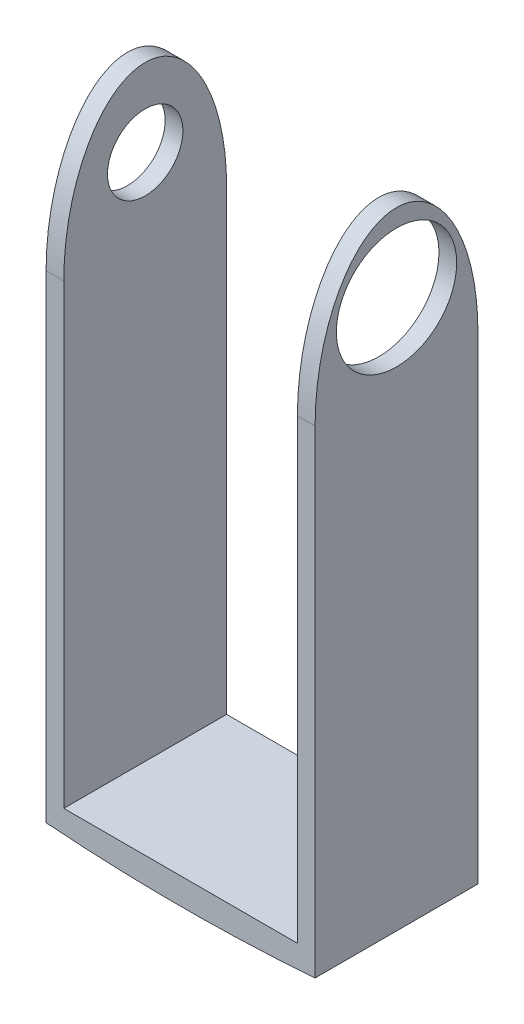
SolidWorks part; units mm, degrees
ref_plane "Front Plane" through (0, 0, 0) normal (0, 0, 1) x (1, 0, 0)
ref_plane "Top Plane" through (0, 0, 0) normal (0, 1, 0) x (1, 0, 0)
ref_plane "Right Plane" through (0, 0, 0) normal (1, 0, 0) x (0, 0, -1)
sketch "Sketch1" plane through (0, 0, 0) normal (0, 0, 1) x (1, 0, 0)
  line L0 (-3.3539, 20.1872) -> (-3.3539, -2.2918)
  line L1 (-3.3539, -2.2918) -> (6.2981, -2.2918)
  line L2 (6.2981, -2.2918) -> (6.2981, 20.1872)
  line L3 (5.6631, 20.1872) -> (5.6631, -1.5298)
  line L4 (5.6631, -1.5298) -> (-2.7189, -1.5298)
  line L5 (-2.7189, -1.5298) -> (-2.7189, 20.1872)
  line L6 (-2.7189, 20.1872) -> (-3.3539, 20.1872)
  line L7 (5.6631, 20.1872) -> (6.2981, 20.1872)
  dimension "D1" = 8.382
  dimension "D2" = 9.652
  dimension "D3" = 0.635
  dimension "D4" = 21.717
  dimension "D5" = 22.479
  dimension "D6" = 21.717
extrude "Boss-Extrude1" add sketch "Sketch1" along normal blind 5.842
sketch "Sketch2" plane through (-3.3539, 0, 0) normal (-1, 0, 0) x (0, 0, 1)
  line L0 (5.842, 20.1872) -> (0, 20.1872) construction
  line L1 (2.921, -2.2918) -> (2.921, 20.1872) construction
  point P0 (2.921, 17.3932)
  point P3 (0, 0)
  point P4 (0, 0)
  point P5 (0, 0)
  point P8 (3.81, 17.3932)
  point P9 (2.54, 17.3932)
  dimension "D1" = 2.794
hole_wizard "#6-32 Tapped Hole1" positions "Sketch3" profile "Sketch4" tap size "#6-32" standard "ANSI Inch" end condition up to next
sketch "Sketch3" plane through (-3.3539, 0, 0) normal (-1, 0, 0) x (0, 0, 1)
  point P0 (2.921, 17.3932)
sketch "Sketch4" plane through (-3.3539, 17.3932, 2.921) normal (0, 1, 0) x (0, 0, 1)
  line L0 (0, 0) -> (0, 0.635)
  line L1 (0, 0.635) -> (1.3525, 0.635)
  line L2 (1.3525, 0.635) -> (1.3525, 0)
  line L5 (1.3525, 0) -> (0, 0)
  line L11 (0, -6.35) -> (0, 107.95) construction
  dimension "Thread Major Dia." = 2.7051
  dimension "Thru Tap Drill Depth" = 0.635
sketch "Sketch5" plane through (6.2981, 0, 0) normal (1, 0, 0) x (0, 0, -1)
  point P0 (-2.921, 17.3932)
  point P1 (0, 0)
sketch "Sketch6" plane through (6.2981, 0, 0) normal (1, 0, 0) x (0, 0, -1)
  circle A0 centre (-2.921, 17.3932) radius 2.159
extrude "Cut-Extrude1" cut sketch "Sketch6" against normal up to next
sketch "Sketch12" plane through (-3.3539, 0, 0) normal (-1, 0, 0) x (0, 0, 1)
  line L0 (2.921, -2.2918) -> (2.921, 20.1872) construction
  line L1 (5.842, -2.2918) -> (0, -2.2918) construction
  line L2 (5.842, 20.1872) -> (0, 20.1872) construction
sketch "Sketch13" plane through (0, 0, 0) normal (0, 0, 1) x (1, 0, 0)
  line L0 (6.2981, -2.2918) -> (1.4721, 60.2603) construction
  line L1 (1.4721, 60.2603) -> (-3.3539, -2.2918) construction
  dimension "D1" = 62.738
  dimension "D2" = 62.738
sketch "Sketch15" plane through (0, 0, 0) normal (0, 0, 1) x (1, 0, 0)
  line L0 (-3.3539, -2.2918) -> (6.2981, -2.2918) construction
  line L1 (6.2981, -2.2918) -> (-3.3539, -2.2918)
  arc A0 (-3.3539, -2.2918) -> (6.2981, -2.2918) centre (1.4721, 60.2603) ccw
extrude "Boss-Extrude2" add sketch "Sketch15" along normal through all
sketch "Sketch18" plane through (-3.3539, 0, 0) normal (-1, 0, 0) x (0, 0, 1)
  line L0 (2.921, -2.2918) -> (2.921, 20.1872) construction
  point P0 (2.921, 11.1176)
  point P1 (2.921, 8.9477)
sketch "Sketch25" plane through (-3.3539, 0, 0) normal (-1, 0, 0) x (0, 0, 1)
  line L0 (2.921, -2.2918) -> (2.921, 20.1872) construction
  point P0 (2.921, 13.3767)
sketch "Sketch28" plane through (6.2981, 0, 0) normal (1, 0, 0) x (0, 0, -1)
  line L0 (-2.921, -2.2918) -> (-2.921, 20.1872) construction
  line L1 (0, 60.2603) -> (0, -2.2918) construction
  line L2 (-5.842, -2.2918) -> (-5.842, 20.1872) construction
  line L3 (-5.842, 14.8606) -> (-5.842, 20.1872)
  line L4 (-5.842, 20.1872) -> (0, 20.1872)
  line L5 (0, 20.1872) -> (0, 14.8606)
  ellipse E0 centre (-2.921, 14.8606) end of major axis (-2.921, 20.1872) minor radius 2.921 (0, 14.8606) -> (-5.842, 14.8606) ccw
  line M6 (0, -2.2918) -> (0, 20.1872)
  line M7 (0, 20.1872) -> (-5.842, 20.1872)
  line M8 (-5.842, 20.1872) -> (-5.842, -2.2918)
extrude "Cut-Extrude4" cut sketch "Sketch28" against normal through all contours E0 L4 M8 | E0 M6 M7 region at (6.2981, 18.9974, 0.6525) region at (6.2981, 18.9974, 5.1895)
